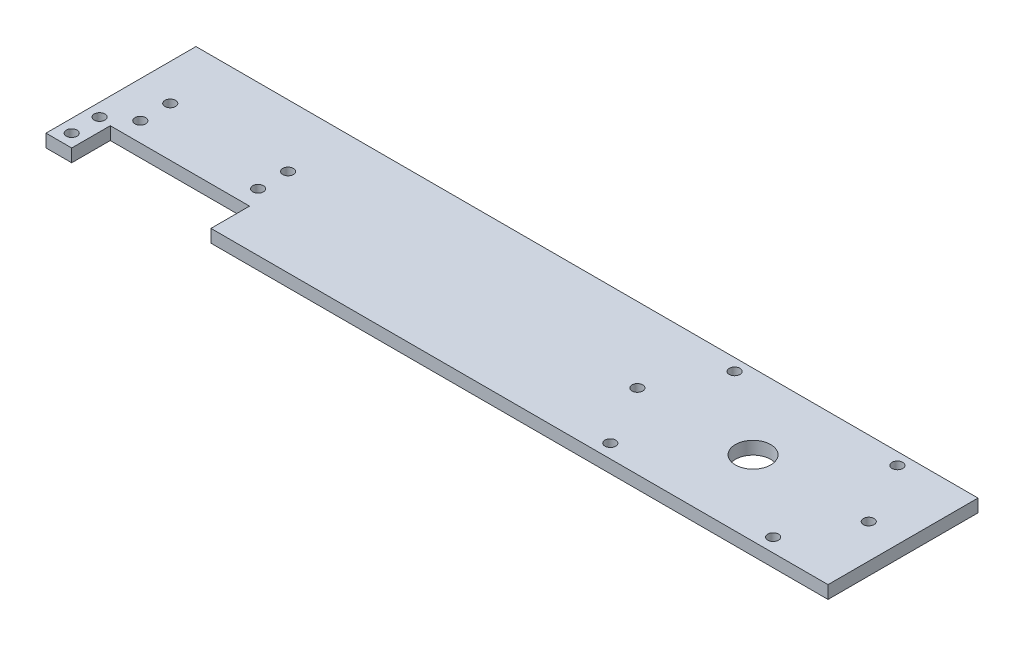
SolidWorks part; units mm, degrees
ref_plane "Front Plane" through (0, 0, 0) normal (0, 0, 1) x (1, 0, 0)
ref_plane "Top Plane" through (0, 0, 0) normal (0, 1, 0) x (1, 0, 0)
ref_plane "Right Plane" through (0, 0, 0) normal (1, 0, 0) x (0, 0, -1)
sketch "Sketch1" plane through (0, 0, 0) normal (0, 1, 0) x (1, 0, 0)
  line L0 (47.5, 13.6856) -> (47.5, -3.2344) construction
  line L1 (-100, 22.5) -> (82.5, 22.5)
  line L2 (-100, 22.5) -> (-100, -12.5)
  line L3 (-100, -12.5) -> (82.5, -12.5)
  line L4 (82.5, 22.5) -> (82.5, -12.5)
  line L6 (12.5, -1) -> (82.5, -1)
  line L7 (12.5, -1) -> (12.5, 11)
  line L8 (12.5, 11) -> (82.5, 11)
  line L9 (82.5, -1) -> (82.5, 11)
  line L10 (12.5, -1) -> (82.5, 11) construction
  line L11 (12.5, 11) -> (82.5, -1) construction
  circle A4 centre (47.5, 5) radius 4.125
  circle A5 centre (74.5, 5) radius 1.25
  circle A6 centre (20.5, 5) radius 1.25
  circle A7 centre (-97, -9.5) radius 1.25
  circle A8 centre (-97, -3) radius 1.25
  circle A9 centre (-91.5, 8) radius 1.25
  circle A10 centre (-64, 8) radius 1.25
  circle A11 centre (-64, 1) radius 1.25
  circle A12 centre (-91.5, 1) radius 1.25
  point P0 (0, 0)
  dimension "D3" = 2.5
  dimension "D4" = 8.25
  dimension "D5" = 2.5
  dimension "D9" = 2.5
  dimension "D13" = 2.5
  dimension "D1" = 35
  dimension "D2" = 182.5
  dimension "D6" = 8
  dimension "D7" = 70
  dimension "D8" = 12
  dimension "D10" = 3
  dimension "D11" = 6.5
  dimension "D12" = 3
  dimension "D14" = 14.5
  dimension "D15" = 8.5
  dimension "D18" = 27.5
  dimension "D16" = 2
  dimension "D17" = 2
extrude "Boss-Extrude1" add sketch "Sketch1" along normal blind 3 contours L7 L8 L4 L1 L2 L3 L6 | L8 L7 L6 L4 A4 A5 A6 region at (-16.9103, 0, -5.0218) region at (81.7898, 0, -5)
sketch "Sketch2" plane through (0, 0, 0) normal (0, 0, 1) x (1, 0, 0)
  line L0 (-94.5, 33) -> (-94.5, -17) construction
  line L1 (-92, 33) -> (-92, -17)
  line L2 (-97, 33) -> (-97, -17)
  line L3 (-89, 33) -> (-89, -17)
  line L4 (-100, 33) -> (-100, -17)
  line L5 (-100, 3) -> (-100, 0) construction
  line L7 (-94, 6.4998) -> (-61.5, 6.4998)
  line L8 (-94, 6.4998) -> (-94, -3.3981)
  line L9 (-94, -3.3981) -> (-61.5, -3.3981)
  line L10 (-61.5, 6.4998) -> (-61.5, -3.3981)
  arc A0 (-92, 33) -> (-97, 33) centre (-94.5, 33) ccw
  arc A1 (-97, -17) -> (-92, -17) centre (-94.5, -17) ccw
  arc A2 (-100, -17) -> (-89, -17) centre (-94.5, -17) ccw
  arc A3 (-89, 33) -> (-100, 33) centre (-94.5, 33) ccw
  point P2 (-94.5, 8)
  dimension "D4" = 5.5
  dimension "D1" = 3
  dimension "D2" = 3
  dimension "D3" = 5
  dimension "D5" = 50
  dimension "D6" = 50
  dimension "D7" = 6
  dimension "D8" = 32.5
extrude "Cut-Extrude3" cut sketch "Sketch2" along normal up to surface (12.5 mm away) from offset 3.5 contours L1 L9 L3 L7 | L10 L7 L3 L9 | L8 L9 L1 L7 region at (-90.5, 1.5509, 0) region at (-93, 1.5509, 0) region at (-75.25, 1.5509, 0) up to face at (-8.75, 1.5, 12.5)
ref_plane "Plane3" through (0, 3, 0) normal (0, -1, 0) x (-1, 0, 0)
sketch "Sketch3" plane through (0, 3, 0) normal (0, -1, 0) x (-1, 0, 0)
  line L0 (-82.5, -12.5) -> (-20.5, -12.5)
  line L2 (-20.5, 5) -> (-20.5, -12.5) construction
  line L3 (-74.5, 5) -> (-74.5, -12.5) construction
  line L5 (-69.5043, 22.7064) -> (-69.5043, -12.2936)
  line L6 (-37.5, -12.5) -> (25.1934, -12.5) construction
  line L7 (-20.5, -12.5) -> (-20.5, 22.5)
  line L8 (100, 22.5) -> (-82.5, 22.5) construction
  line L9 (-20.5, 22.5) -> (-82.5, 22.5)
  line L10 (-25.5, 22.5) -> (-25.5, -12.5)
  line L11 (-69.5043, 22.7064) -> (-25.5, 22.5)
  line L12 (-69.5043, -12.2936) -> (-25.5, -12.5)
  circle A4 centre (-66.5, -9.3076) radius 1.25
  circle A5 centre (-28.5, -9.3076) radius 1.25
  circle A6 centre (-28.5, 19.6924) radius 1.25
  circle A7 centre (-66.5, 19.6924) radius 1.25
  point P14 (-69.5043, 5.2064)
  dimension "D3" = 35
  dimension "D4" = 5
  dimension "D8" = 8
  dimension "D14" = 2.5
  dimension "D1" = 54
  dimension "D2" = 5
  dimension "D5" = 62
  dimension "D6" = 54
  dimension "D7" = 44.0043
  dimension "D9" = 3.0043
  dimension "D10" = 3
  dimension "D13" = 3
  dimension "D11" = 2
  dimension "D12" = 2
extrude "Cut-Extrude7" cut sketch "Sketch3" along normal blind 10 contours A4 | A7 | A6 | A5 region at (66.5, 3, 9.3076)
